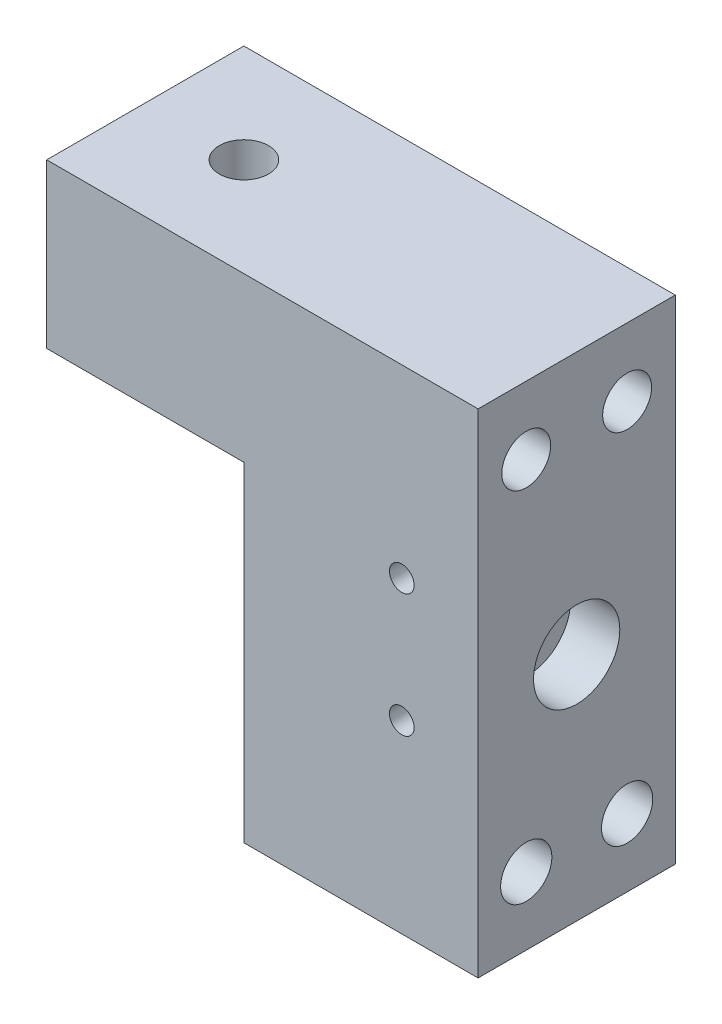
SolidWorks part; units mm, degrees
material "McMaster 6061-T6"
ref_plane "Front Plane" through (0, 0, 0) normal (0, 0, 1) x (1, 0, 0)
ref_plane "Top Plane" through (0, 0, 0) normal (0, 1, 0) x (1, 0, 0)
ref_plane "Right Plane" through (0, 0, 0) normal (1, 0, 0) x (0, 0, -1)
sketch "Sketch2" plane through (0, 0, 0) normal (1, 0, 0) x (0, 0, -1)
  line L1 (-212.3494, -348.1117) -> (-237.7494, -348.1117)
  line L2 (-212.3494, -348.1117) -> (-212.3494, -411.6117)
  line L3 (-212.3494, -411.6117) -> (-237.7494, -411.6117)
  line L4 (-237.7494, -348.1117) -> (-237.7494, -411.6117)
  dimension "D1" = 25.4
  dimension "D2" = 63.5
extrude "Boss-Extrude1" add sketch "Sketch2" against normal up to surface (30.176 mm away)
sketch "Sketch3" plane through (-30.176, 0, 0) normal (-1, 0, 0) x (0, 0, 1)
  line L0 (212.3494, -348.1117) -> (212.3494, -411.6117) construction
  line L1 (237.7494, -348.1117) -> (212.3494, -348.1117)
  line L2 (237.7494, -348.1117) -> (237.7494, -369.1617)
  line L3 (237.7494, -369.1617) -> (212.3494, -369.1617)
  line L4 (212.3494, -348.1117) -> (212.3494, -369.1617)
  line L5 (56.1388, -369.1617) -> (707.4994, -369.1617) construction
extrude "Boss-Extrude2" add sketch "Sketch3" along normal blind 25.4
sketch "Sketch6" plane through (0, -348.1117, 0) normal (0, 1, 0) x (1, 0, 0)
  line L0 (-42.876, -237.7494) -> (-42.876, -212.3494) construction
  line L1 (-55.576, -237.7494) -> (0, -237.7494) construction
  line L2 (-55.576, -212.3494) -> (0, -212.3494) construction
  line L3 (-55.576, -237.7494) -> (-55.576, -212.3494) construction
  point P8 (-42.876, -225.0494)
  dimension "D1" = 12.7
hole_wizard "1/4 (0.25) Diameter Hole1" positions "Sketch7" profile "Sketch9" hole size "1/4" standard "ANSI Inch" end condition through all
sketch "Sketch7" plane through (0, -348.1117, 0) normal (0, 1, 0) x (1, 0, 0)
  point P0 (-42.876, -225.0494)
sketch "Sketch9" plane through (-42.876, -348.1117, 225.0494) normal (1, 0, 0) x (0, 0, 1)
  line L0 (0, 0) -> (0, 63.5)
  line L1 (0, 63.5) -> (3.175, 63.5)
  line L2 (3.175, 63.5) -> (3.175, 0)
  line L5 (3.175, 0) -> (0, 0)
  line L11 (0, -6.35) -> (0, 107.95) construction
  dimension "Thru Hole Dia." = 6.35
  dimension "Thru Hole Depth" = 63.5
hole_wizard "CBORE for M6 Hex Head Bolt1" positions "Sketch10" profile "Sketch11" counterbore size "M6" standard "ANSI Metric" end condition through all
sketch "Sketch10" plane through (-30.176, 0, 0) normal (-1, 0, 0) x (0, 0, 1)
  point P0 (231.5494, -402.8617)
  point P3 (218.5494, -402.8617)
sketch "Sketch11" plane through (-30.176, -402.8617, 231.5494) normal (0, 1, 0) x (0, 0, 1)
  line L0 (0, 0) -> (0, 30.176)
  line L1 (0, 30.176) -> (3.3, 30.176)
  line L3 (3.3, 30.176) -> (3.3, 4.38)
  line L4 (3.3, 4.38) -> (5, 4.38)
  line L5 (5, 4.38) -> (5, 0)
  line L7 (5, 0) -> (0, 0)
  line L11 (0, -6.35) -> (0, 107.95) construction
  dimension "Thru Hole Dia." = 6.6
  dimension "Thru Hole Depth" = 30.176
  dimension "C'Bore Dia." = 10
  dimension "C'Bore Depth" = 4.38
hole_wizard "Ø1.0mm Dowel Hole1" positions "Sketch12" profile "Sketch13" hole size "Ø1.0" standard "ANSI Metric"
sketch "Sketch12" plane through (0, 0, 0) normal (1, 0, 0) x (0, 0, -1)
  point P0 (-231.5494, -356.8617)
  point P3 (-218.5494, -356.8617)
sketch "Sketch13" plane through (0, -356.8617, 231.5494) normal (0, 1, 0) x (0, 0, -1)
  line L0 (0, 0) -> (0, 10.8927)
  line L1 (0, 10.8927) -> (3.15, 9)
  line L2 (3.15, 9) -> (3.15, 0)
  line L5 (3.15, 0) -> (0, 0)
  line L10 (0, 10.8927) -> (-3.15, 9) construction
  line L11 (0, -6.35) -> (0, 107.95) construction
  dimension "Hole Dia." = 6.3
  dimension "Hole Depth" = 9
  dimension "Drill Angle" = 118
hole_wizard "1/8 (0.125) Diameter Hole1" positions "Sketch14" profile "Sketch15" hole size "1/8" standard "ANSI Inch" end condition through all
sketch "Sketch14" plane through (0, 0, 212.3494) normal (0, 0, -1) x (-1, 0, 0)
  point P0 (9.8313, -371.9242)
  point P3 (9.8313, -387.7992)
sketch "Sketch15" plane through (-9.8313, -371.9242, 212.3494) normal (1, 0, 0) x (0, 1, 0)
  line L0 (0, 0) -> (0, 25.4)
  line L1 (0, 25.4) -> (1.5875, 25.4)
  line L2 (1.5875, 25.4) -> (1.5875, 0)
  line L5 (1.5875, 0) -> (0, 0)
  line L11 (0, -6.35) -> (0, 107.95) construction
  dimension "Thru Hole Dia." = 3.175
  dimension "Thru Hole Depth" = 25.4
sketch "Sketch16" plane through (0, 0, 0) normal (1, 0, 0) x (0, 0, -1)
  line L0 (-237.7494, -381.8617) -> (-212.3494, -381.8617) construction
  line L1 (-237.7494, -348.1117) -> (-237.7494, -411.6117) construction
  line L2 (-212.3494, -411.6117) -> (-212.3494, -348.1117) construction
  line L3 (-212.3494, -388.3365) -> (-212.3494, -375.3869) construction
  point P8 (-212.3494, -381.8617)
  point P9 (-225.0494, -381.8617)
hole_wizard "CBORE for #10 Binding Head Machine Screw1" positions "Sketch17" profile "Sketch18" counterbore size "#10" standard "ANSI Inch" end condition up to next
sketch "Sketch17" plane through (0, 0, 0) normal (1, 0, 0) x (0, 0, -1)
  line L0 (-212.3494, -381.8617) -> (-237.7494, -381.8617) construction
  line L1 (-212.3494, -411.6117) -> (-212.3494, -348.1117) construction
  line L2 (-237.7494, -348.1117) -> (-237.7494, -411.6117) construction
  line L4 (-212.3494, -388.3365) -> (-212.3494, -375.3869) construction
  point P0 (-225.0494, -381.8617)
  point P13 (-212.3494, -381.8617)
sketch "Sketch18" plane through (0, -381.8617, 225.0494) normal (0, 1, 0) x (0, 0, -1)
  line L0 (0, 0) -> (0, 30.176)
  line L1 (0, 30.176) -> (2.5527, 30.176)
  line L3 (2.5527, 30.176) -> (2.5527, 6.35)
  line L4 (2.5527, 6.35) -> (5.5562, 6.35)
  line L5 (5.5562, 6.35) -> (5.5562, 0)
  line L7 (5.5562, 0) -> (0, 0)
  line L11 (0, -6.35) -> (0, 107.95) construction
  dimension "Thru Hole Dia." = 5.1054
  dimension "Thru Hole Depth" = 30.176
  dimension "C'Bore Dia." = 11.1125
  dimension "C'Bore Depth" = 6.35
